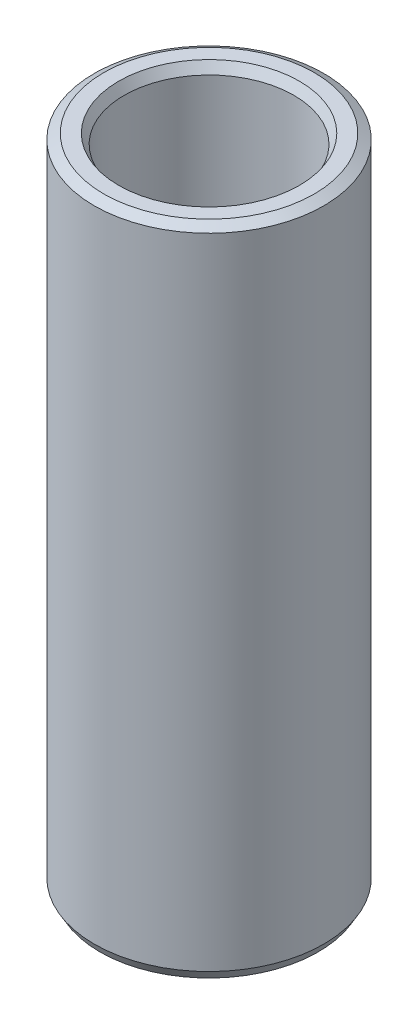
SolidWorks part; units mm, degrees
ref_plane "Front Plane" through (0, 0, 0) normal (0, 0, 1) x (1, 0, 0)
ref_plane "Top Plane" through (0, 0, 0) normal (0, 1, 0) x (1, 0, 0)
ref_plane "Right Plane" through (0, 0, 0) normal (1, 0, 0) x (0, 0, -1)
sketch "Sketch1" plane through (0, 0, 0) normal (0, 1, 0) x (1, 0, 0)
  circle A0 centre (0, 0) radius 50
  dimension "SLEEVE_OD" = 100
extrude "Boss-Extrude1" add sketch "Sketch1" along normal blind 285.1692
sketch "Sketch2" plane through (0, 0, 0) normal (0, 1, 0) x (1, 0, 0)
  circle A0 centre (0, 0) radius 36.9739
  dimension "BORE_D" = 73.9478
extrude "Cut-Extrude1" cut sketch "Sketch2" along normal through all
chamfer "Chamfer1" distance 2.3932 angle 60 4 edges at (0, 285.1692, 36.9739) (0, 0, 36.9739) (0, 0, 50) (0, 285.1692, 50) first distance on face at (0, 285.1692, 36.9739) first distance on face at (0, 0, 36.9739) first distance on face at (0, 285.1692, 50)
